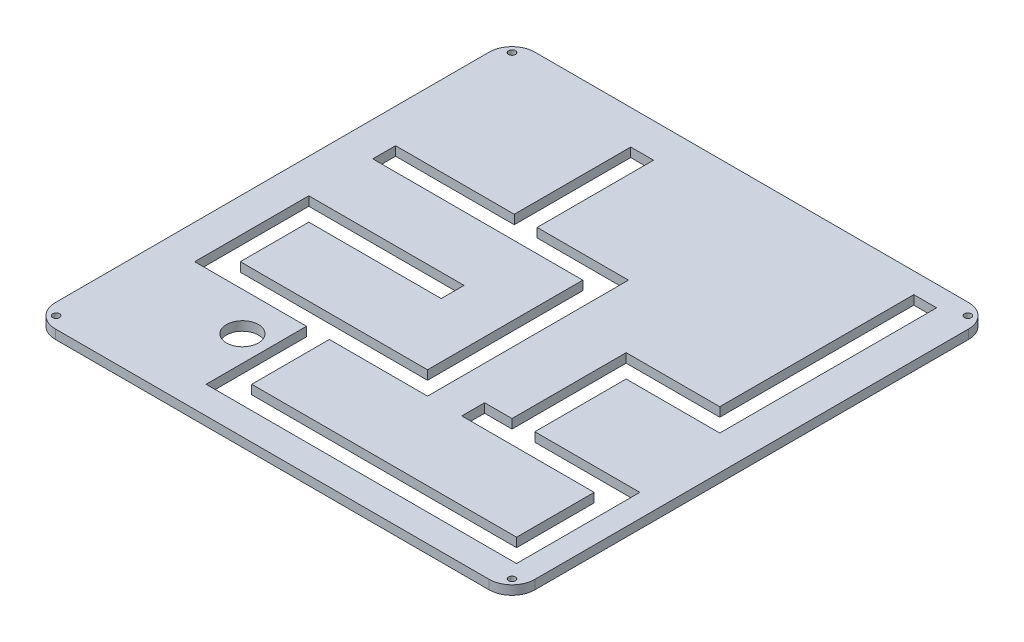
SolidWorks part; units mm, degrees
ref_plane "Front Plane" through (0, 0, 0) normal (0, 0, 1) x (1, 0, 0)
ref_plane "Top Plane" through (0, 0, 0) normal (0, 1, 0) x (1, 0, 0)
ref_plane "Right Plane" through (0, 0, 0) normal (1, 0, 0) x (0, 0, -1)
sketch "Sketch1" plane through (0, 0, 0) normal (0, 1, 0) x (1, 0, 0)
  line L0 (-101, -101) -> (-101, 101)
  line L5 (-105, -105) -> (105, -105)
  line L6 (-105, -105) -> (-105, 105)
  line L7 (-105, 105) -> (105, 105)
  line L8 (105, -105) -> (105, 105)
  line L9 (-101, 101) -> (101, 101)
  line L10 (101, -101) -> (101, 101)
  line L11 (-101, -101) -> (101, -101)
  line L12 (-101, 101) -> (-99.8333, 99.8333) construction
  line L13 (-55, 0) -> (55, 0) construction
  line L14 (-101, -101) -> (-99.8333, -99.8333) construction
  line L15 (0, -55) -> (0, 55) construction
  line L16 (101, -101) -> (99.8333, -99.8333) construction
  line L17 (101, 101) -> (99.8333, 99.8333) construction
  circle A1 centre (-99.8333, 99.8333) radius 1.5
  circle A2 centre (-99.8333, -99.8333) radius 1.5
  circle A3 centre (99.8333, -99.8333) radius 1.5
  circle A4 centre (99.8333, 99.8333) radius 1.5
  point P0 (0, 0)
  point P6 (-105, 0)
  point P7 (0, 105)
  dimension "D3" = 4
  dimension "D4" = 3
  dimension "D1" = 210
  dimension "D2" = 210
  dimension "D5" = 1.65
  dimension "D6" = 45
extrude "MainExtrude" add sketch "Sketch1" along normal blind 4 contours L6 L5 L8 L7
extrude "ScrewHoles" cut sketch "Sketch1<6>" along normal up to surface (4 mm away) contours A1 | A2 | A3 | A4 up to face at (0, 4, 0)
sketch "Sketch1<6>" plane through (0, 0, 0) normal (0, 1, 0) x (1, 0, 0) same geometry as "Sketch1"
fillet "RoundedCorners" radius 10 4 edges at (-105, 2, -105) (-105, 2, 105) (105, 2, -105) (105, 2, 105)
sketch "Sketch3" plane through (0, 0, 0) normal (0, 1, 0) x (1, 0, 0)
  line L24 (-33, 90) -> (-33, 39) construction
  line L25 (-38, 90) -> (-38, 39)
  line L58 (-90, 34) -> (7, 34) construction
  line L59 (7, 34) -> (7, -44) construction
  line L60 (7, -44) -> (-85, -44) construction
  line L61 (-85, -44) -> (-85, -4) construction
  line L62 (-85, -4) -> (-22, -4) construction
  line L63 (-36, -49) -> (-36, -88) construction
  line L64 (-36, -88) -> (90, -88) construction
  line L65 (90, -88) -> (90, -44) construction
  line L66 (90, -44) -> (27, -44) construction
  line L68 (-90, 29) -> (2, 29)
  line L69 (2, 29) -> (2, -39)
  line L70 (2, -39) -> (-80, -39)
  line L71 (-80, -39) -> (-80, -9)
  line L72 (-80, -9) -> (-22, -9)
  line L73 (-41, -49) -> (-41, -93)
  line L74 (-41, -93) -> (95, -93)
  line L75 (95, -93) -> (95, -39)
  line L76 (95, -39) -> (49, -39)
  line L77 (-28, 90) -> (-28, 39)
  line L78 (-90, 39) -> (-38, 39)
  line L79 (12, 39) -> (12, -49)
  line L80 (12, -49) -> (-31, -49)
  line L81 (-90, -49) -> (-90, 1)
  line L82 (-90, 1) -> (-22, 1)
  line L83 (-31, -49) -> (-31, -83)
  line L84 (-31, -83) -> (85, -83)
  line L85 (85, -83) -> (85, -49)
  line L86 (85, -49) -> (27, -49)
  line L87 (-38, 90) -> (-28, 90)
  line L89 (-90, 29) -> (-90, 39)
  line L90 (-22, -9) -> (-22, 1)
  line L92 (27, -39) -> (27, -49)
  line L93 (-28, 90) -> (-28, 12.6574) construction
  line L94 (-33, 90) -> (-33, 12.6574) construction
  line L95 (-38, 90) -> (-38, 12.6574) construction
  line L96 (-31, 33.5948) -> (-31, -83) construction
  line L97 (-36, 33.5948) -> (-36, -88) construction
  line L98 (-41, 33.5948) -> (-41, -93) construction
  line L99 (-41, -49) -> (-90, -49)
  line L100 (12, -49) -> (-90, -49) construction
  line L101 (-28, 39) -> (12, 39)
  line L102 (-90, 39) -> (12, 39) construction
  line L106 (44, -39) -> (44, 6) construction
  line L107 (44, 6) -> (85, 6) construction
  line L108 (85, 6) -> (85, 96) construction
  line L109 (49, -39) -> (49, 1)
  line L110 (49, 1) -> (90, 1)
  line L111 (-12.3092, 87.9178) -> (68.6908, 87.9178) construction
  line L112 (-12.3092, 87.9178) -> (-12.3092, 44.9178) construction
  line L113 (-12.3092, 44.9178) -> (68.6908, 44.9178) construction
  line L114 (68.6908, 87.9178) -> (68.6908, 44.9178) construction
  line L115 (90, 1) -> (90, 96)
  line L116 (39, -39) -> (39, 11)
  line L117 (39, 11) -> (80, 11)
  line L118 (80, 11) -> (80, 96)
  line L120 (90, 96) -> (80, 96)
  line L121 (39, -39) -> (27, -39)
  line L122 (95, -39) -> (27, -39) construction
  line L123 (105, -95) -> (105, 95) construction
  line L124 (-105, -95) -> (-105, 95) construction
  line L125 (-95, 105) -> (95, 105) construction
  line L126 (-95, -105) -> (95, -105) construction
  circle A1 centre (-52.2057, -65.8684) radius 7
  dimension "D18" = 14
  dimension "D1" = 5
  dimension "D2" = 5
  dimension "D3" = 68
  dimension "D4" = 5
  dimension "D5" = 5
  dimension "D6" = 34
  dimension "D7" = 51
  dimension "D8" = 102
  dimension "D9" = 68
  dimension "D11" = 68
  dimension "D13" = 30
  dimension "D14" = 136
  dimension "D10" = 34
  dimension "D12" = 40
  dimension "D15" = 51
  dimension "D17" = 102
  dimension "D16" = 85
  dimension "D19" = 43
  dimension "D20" = 81
  dimension "D21" = 15
  dimension "D22" = 15
  dimension "D23" = 15
  dimension "D24" = 12
  dimension "D25" = 15
  dimension "D26" = 108
extrude "Trench" cut sketch "Sketch3" along normal blind 4
equation "\"1_LED\"= 17mm"
equation "\"2_LED\"= \"1_LED\" * 2"
equation "\"3_LED\"= \"1_LED\" * 3"
equation "\"4_LED\"= \"1_LED\" * 4"
equation "\"5_LED\"= \"1_LED\" * 5"
equation "\"6_LED\"= \"1_LED\" * 6"
equation "\"7_LED\"= \"1_LED\" * 7"
equation "\"8_LED\"= \"1_LED\" * 8"
equation "\"9_LED\"= \"1_LED\" * 9"
equation "\"10_LED\"= \"1_LED\" * 10"
equation "\"11_LED\"= \"1_LED\" * 11"
equation "\"12_LED\"= \"1_LED\" * 12"
